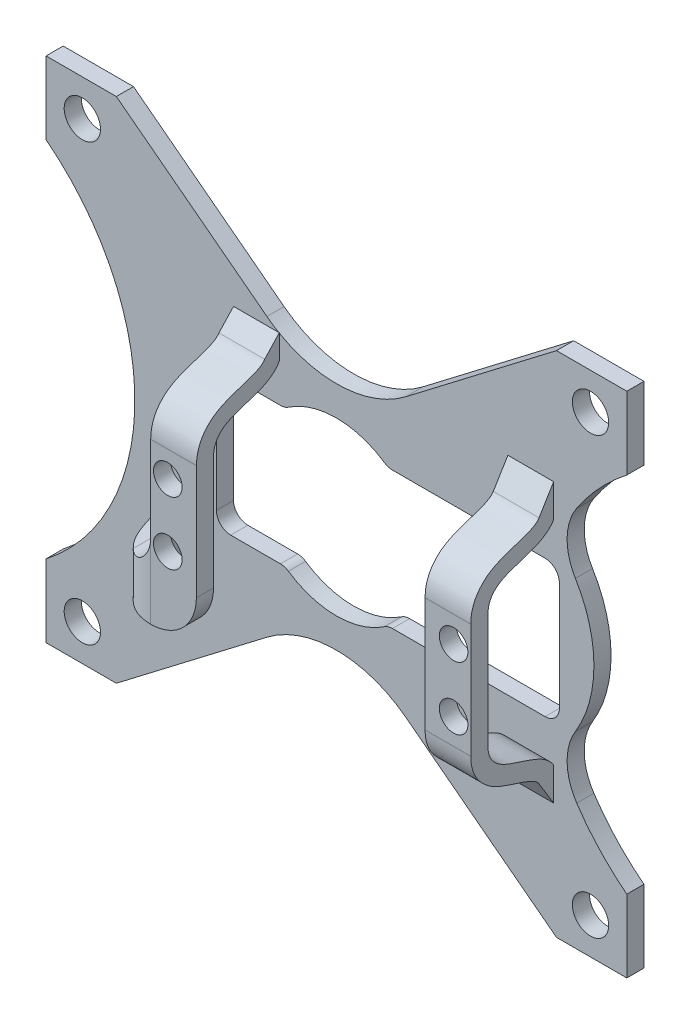
SolidWorks part; units mm, degrees
ref_plane "Front Plane" through (0, 0, 0) normal (0, 0, 1) x (1, 0, 0)
ref_plane "Top Plane" through (0, 0, 0) normal (0, 1, 0) x (1, 0, 0)
ref_plane "Right Plane" through (0, 0, 0) normal (1, 0, 0) x (0, 0, -1)
sketch "Sketch1" plane through (0, 0, 0) normal (0, 0, 1) x (1, 0, 0)
  line L0 (41.275, 31.75) -> (41.275, -31.75) construction
  line L1 (-73.025, -44.45) -> (53.975, -44.45)
  line L2 (-73.025, -44.45) -> (-73.025, 44.45)
  line L3 (-73.025, 44.45) -> (53.975, 44.45)
  line L4 (53.975, -44.45) -> (53.975, 44.45)
  line L5 (-73.025, -44.45) -> (53.975, 44.45) construction
  line L6 (-73.025, 44.45) -> (53.975, -44.45) construction
  line L7 (28.975, 44.45) -> (2.6263, 24.295)
  line L12 (-9.525, 44.45) -> (-9.525, 15) construction
  line L13 (41.275, 44.45) -> (41.275, 31.75)
  line L14 (41.275, -44.45) -> (41.275, -31.75)
  line L15 (-60.325, -44.45) -> (-60.325, -31.75)
  line L16 (-60.325, 44.45) -> (-60.325, 31.75)
  line L17 (53.975, 0) -> (3.975, 0) construction
  line L18 (-48.025, 44.45) -> (-21.6763, 24.295)
  line L19 (-48.025, -44.45) -> (-21.6763, -24.295)
  line L20 (28.975, -44.45) -> (2.6263, -24.295)
  line L22 (-30.525, -12) -> (-18.525, -12)
  line L23 (-30.525, -12) -> (-30.525, 12)
  line L24 (-30.525, 12) -> (-18.525, 12)
  line L25 (-18.525, -12) -> (-18.525, 12)
  line L28 (-0.525, -12) -> (29.475, -12)
  line L29 (-0.525, -12) -> (-0.525, 12)
  line L30 (-0.525, 12) -> (29.475, 12)
  line L31 (29.475, -12) -> (29.475, 12)
  circle A0 centre (34.925, 38.1) radius 3.175
  circle A1 centre (-53.975, 38.1) radius 3.175
  circle A2 centre (-66.675, 25.4) radius 3.175
  circle A3 centre (-66.675, -25.4) radius 3.175
  circle A4 centre (-53.975, -38.1) radius 3.175
  circle A5 centre (34.925, -38.1) radius 3.175
  circle A6 centre (47.625, -25.4) radius 3.175
  circle A7 centre (47.625, 25.4) radius 3.175
  circle A8 centre (-9.525, 0) radius 15
  arc A9 (41.275, 31.75) -> (32.5128, 22.3351) centre (65.9507, 0) ccw
  arc A10 (41.275, -31.75) -> (32.5128, -22.3351) centre (65.9507, 0) cw
  arc A11 (-60.325, -31.75) -> (-44.7894, 0) centre (-85.0007, 0) ccw
  arc A12 (-60.325, 31.75) -> (-44.7894, 0) centre (-85.0007, 0) cw
  arc A13 (2.6263, 24.295) -> (-21.6763, 24.295) centre (-9.525, 40.1804) cw
  arc A14 (2.6263, -24.295) -> (-21.6763, -24.295) centre (-9.525, -40.1804) ccw
  arc A15 (32.2789, -11.5934) -> (32.2789, 11.5934) centre (13.1715, 0) ccw
  arc A16 (32.2789, 11.5934) -> (32.5128, 22.3351) centre (40.8283, 16.7807) cw
  arc A17 (32.2789, -11.5934) -> (32.5128, -22.3351) centre (40.8283, -16.7807) ccw
  point P0 (-9.525, 0)
  point P45 (0, 0)
  point P54 (0, 0)
  dimension "D3" = 30
  dimension "D8" = 88.9
  dimension "D9" = 25
  dimension "D5" = 50
  dimension "D13" = 20
  dimension "D15" = 10
  dimension "D1" = 127
  dimension "D2" = 6.35
  dimension "D4" = 15
  dimension "D7" = 19.05
  dimension "D10" = 12.7
  dimension "D6" = 6.35
  dimension "D11" = 12.7
  dimension "D12" = 12.7
  dimension "D14" = 12
extrude "Boss-Extrude1" add sketch "Sketch1" along normal blind 3 contours L4 L3 L2 L1 A8 A7 A6 A5 A4 A3 A2 A1 A0 region at (-58.975, -38.1, 0)
sketch "Sketch2" plane through (20.475, 0, 0) normal (1, 0, 0) x (0, 1, 0)
  line L0 (10, 44.6) -> (10, 14) construction
  line L1 (10, 14.5) -> (-10, 14.5)
  line L2 (10, 14.5) -> (10, 17.5)
  line L3 (10, 17.5) -> (-10, 17.5)
  line L4 (-10, 14.5) -> (-10, 17.5)
  line L5 (-10, 44.6) -> (-10, 14) construction
  line L7 (0, 17.5) -> (0, 14.5) construction
  line L8 (18.5899, 3) -> (24.3467, 3)
  line L9 (20.1533, 5.5604) -> (24.3467, 3)
  line L11 (-20.1533, 5.5604) -> (-24.3467, 3)
  line L12 (-18.5899, 3) -> (-24.3467, 3)
  line L13 (10, 14.5) -> (10, 17.5)
  line L16 (10.0308, 17.4998) -> (10, 17.5)
  line L17 (-10, 17.5) -> (-10.0308, 17.4998)
  line L18 (31.75, 3) -> (22.3351, 3) construction
  spline S0 degree 3 poles (10, 14.5) (16.0446, 14.4379) (14.1847, 5.6897) (18.5899, 3) knots 0 0 0 0 1 1 1 1
  spline S1 degree 1 poles (10.0308, 17.4998) (20.1533, 5.5604) knots 0 0 1 1 construction
  spline S2 degree 3 poles (10.0308, 17.4998) (10.5803, 17.4942) (11.6908, 17.3812) (13.7449, 16.6992) (15.7401, 15.0501) (17.0126, 12.7979) (17.7868, 10.6515) (18.3801, 8.6858) (18.9697, 7.0604) (19.4886, 6.1722) (19.8692, 5.7606) (20.0511, 5.6229) (20.1533, 5.5604) knots 0 0 0 0 0.0625 0.125 0.25 0.375 0.5 0.625 0.75 0.875 0.9375 1 1 1 1
  spline S3 degree 3 poles (-10, 14.5) (-16.0446, 14.4379) (-14.1847, 5.6897) (-18.5899, 3) knots 0 0 0 0 1 1 1 1
  spline S4 degree 3 poles (-10.0308, 17.4998) (-10.5803, 17.4942) (-11.6908, 17.3812) (-13.7449, 16.6992) (-15.7401, 15.0501) (-17.0126, 12.7979) (-17.7868, 10.6515) (-18.3801, 8.6858) (-18.9697, 7.0604) (-19.4886, 6.1722) (-19.8692, 5.7606) (-20.0511, 5.6229) (-20.1533, 5.5604) knots 0 0 0 0 0.0625 0.125 0.25 0.375 0.5 0.625 0.75 0.875 0.9375 1 1 1 1
  line M4 (10, 14) -> (10, 44.6)
  line M6 (-10, 44.6) -> (-10, 14)
  dimension "D2" = 3
  dimension "D3" = 3
  dimension "D4" = 1.3736
extrude "Boss-Extrude2" add sketch "Sketch2" along normal blind 8 contours S2 L16 S0 L8 L9 M4 | L3 L1 M4 M6 | L17 S4 L11 L12 S3 M6 region at (20.475, 0, 16) region at (20.475, 16.1443, 10.0739) region at (20.475, -16.1443, 10.074)
sketch "Sketch3" plane through (-19.525, 0, 0) normal (-1, 0, 0) x (0, 0, 1)
  line L3 (44.6, -10) -> (14, -10) construction
  line L4 (14.5, 10) -> (14.5, -10) construction
  line L8 (44.6, 10) -> (14, 10) construction
  line L10 (14.5, -10) -> (14.5, 10)
  line L11 (14.5, -10) -> (17.5, -10)
  line L12 (17.5, -10) -> (17.5, 10)
  line L13 (14.5, 10) -> (17.5, 10)
  line L14 (17.5, 0) -> (14.5, 0) construction
  line L15 (5.5516, 20.1677) -> (3, 22.9059)
  line L16 (3, 18.6097) -> (3, 22.9059)
  line L17 (14.5, -10) -> (17.5, -10)
  line L18 (17.491, -10.0452) -> (17.5, -10)
  line L19 (17.5, 10) -> (17.491, 10.0452)
  line L21 (3, 20.1804) -> (3, 24.295) construction
  spline S2 degree 3 poles (14.5, 10) (14.3156, 16.0357) (5.4935, 14.0529) (3, 18.6097) knots 0 0 0 0 1 1 1 1
  spline S3 degree 3 poles (17.491, 10.0452) (17.4854, 10.5947) (17.3724, 11.7053) (16.6904, 13.7593) (15.0413, 15.7545) (12.7891, 17.0271) (10.6427, 17.8012) (8.677, 18.3945) (7.0516, 18.9842) (6.1634, 19.503) (5.7518, 19.8837) (5.614, 20.0655) (5.5516, 20.1677) knots 0 0 0 0 0.0625 0.125 0.25 0.375 0.5 0.625 0.75 0.875 0.9375 1 1 1 1
  line M9 (14, -10) -> (44.6, -10)
  line M11 (44.6, 10) -> (14, 10)
  dimension "D2" = 3
extrude "Boss-Extrude3" add sketch "Sketch3" along normal blind 8 contours L14 L12 L10 M11 | L12 L14 L10 M9 | L19 S3 L15 L16 S2 M11 region at (-19.525, -5, 16) region at (-19.525, 5, 16) region at (-19.525, 15.9151, 10.2632)
sketch "Sketch4" plane through (0, 0, 14.5) normal (0, 0, -1) x (-1, 0, 0)
  line L0 (27.525, -18) -> (27.525, -10)
  line L1 (19.525, -10) -> (27.525, -10)
  arc A0 (19.525, -10) -> (27.525, -18) centre (27.525, -10) ccw
extrude "Boss-Extrude4" add sketch "Sketch4" against normal up to surface (3 mm away) up to face at (-23.525, 0, 17.5)
sketch "Sketch5" plane through (0, -10, 0) normal (0, -1, 0) x (1, 0, 0)
  line L1 (-37.6475, 5.5606) -> (-40.424, 3.033)
  line L3 (-36.1279, 3.033) -> (-40.424, 3.033)
  line L13 (-27.525, 14.5) -> (-27.525, 17.5)
  spline S0 degree 3 poles (-27.525, 14.5) (-33.5704, 14.3814) (-31.5741, 5.5189) (-36.1279, 3.033) knots 0 0 0 0 1 1 1 1
  spline S1 degree 3 poles (-27.525, 17.5) (-28.0745, 17.4944) (-29.185, 17.3813) (-31.2391, 16.6994) (-33.2343, 15.0502) (-34.5068, 12.7981) (-35.2809, 10.6516) (-35.8743, 8.686) (-36.4639, 7.0606) (-36.9828, 6.1724) (-37.3634, 5.7608) (-37.5453, 5.623) (-37.6475, 5.5606) knots 0 0 0 0 0.0625 0.125 0.25 0.375 0.5 0.625 0.75 0.875 0.9375 1 1 1 1
extrude "Boss-Extrude5" add sketch "Sketch5" along normal blind 8
fillet "Fillet1" radius 5 1 edges
fillet "Fillet2" radius 2.5 8 edges at (-18.525, -12, 1.5) (-30.525, -12, 1.5) (-30.525, 12, 1.5) (-18.525, 12, 1.5) (-0.525, 12, 1.5) (29.475, 12, 1.5) (29.475, -12, 1.5) (-0.525, -12, 1.5)
sketch "Sketch6" plane through (0, 0, 14.5) normal (0, 0, -1) x (-1, 0, 0)
  circle A0 centre (24.525, -5.5) radius 2.5
  circle A1 centre (24.525, 5.5) radius 2.5
  circle A2 centre (-25.475, -5.5) radius 2.5
  circle A3 centre (-25.475, 5.5) radius 2.5
  arc A4 (-27.475, 4) -> (-27.475, 7) centre (-25.475, 5.5) ccw construction
  arc A5 (-27.475, -7) -> (-27.475, -4) centre (-25.475, -5.5) ccw construction
  dimension "D1" = 5
extrude "Cut-Extrude1" cut sketch "Sketch6" against normal blind 10
